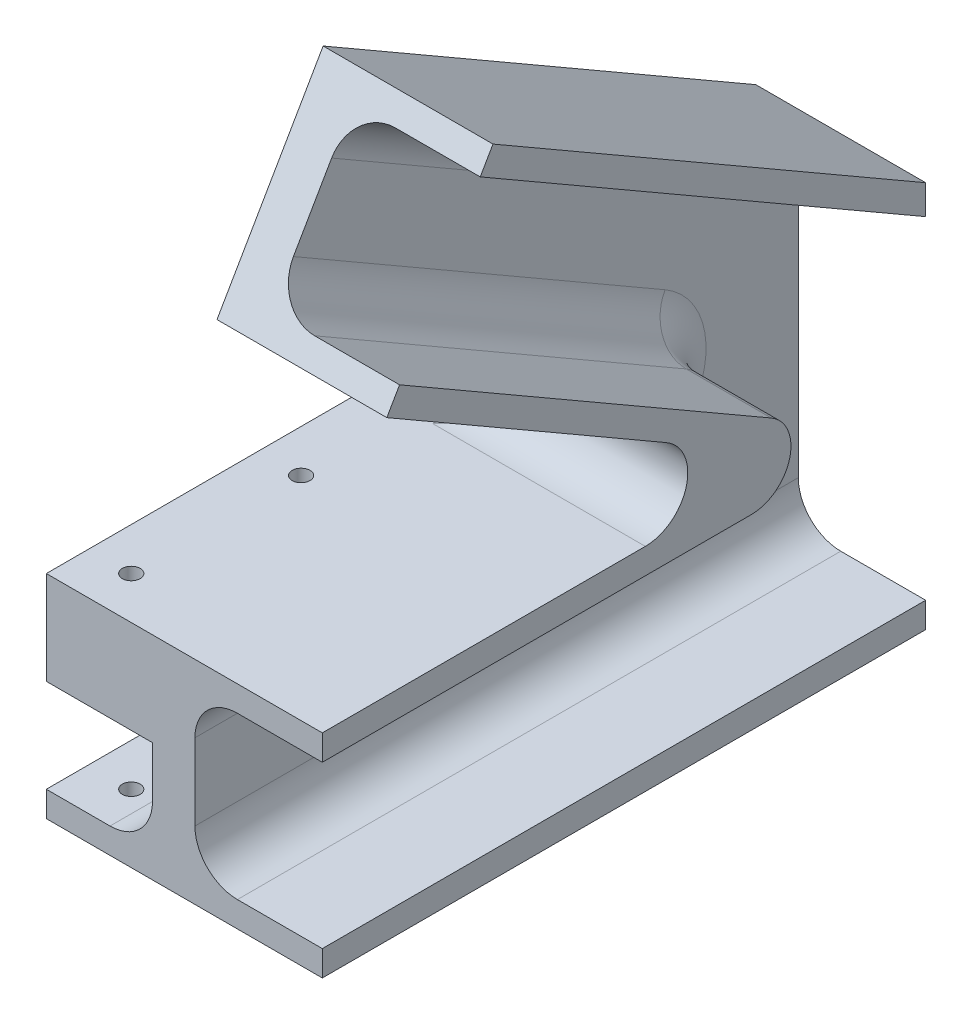
SolidWorks part; units mm, degrees
ref_plane "前视基准面" through (0, 0, 0) normal (0, 0, 1) x (1, 0, 0)
ref_plane "上视基准面" through (0, 0, 0) normal (0, 1, 0) x (1, 0, 0)
ref_plane "右视基准面" through (0, 0, 0) normal (1, 0, 0) x (0, 0, -1)
sketch "草图1" plane through (0, 0, 0) normal (1, 0, 0) x (0, 0, -1)
  line L0 (0, 0) -> (113.3975, 0)
  line L1 (113.3975, 0) -> (15.1924, 56.6987)
  line L2 (0, -50) -> (300, -50)
  line L3 (300, -50) -> (40.1924, 100)
  line L4 (0, 0) -> (0, -50)
  line L5 (40.1924, 100) -> (15.1924, 56.6987)
  line L6 (230.718, -10) -> (230.718, -50)
  line L7 (6, -6) -> (135.7898, -6)
  line L8 (135.7898, -6) -> (23.3885, 58.8949)
  line L10 (277.6077, -44) -> (42.3885, 91.8038)
  line L11 (6, -44) -> (277.6077, -44)
  line L13 (6, -6) -> (6, -44) construction
  line L14 (42.3885, 91.8038) -> (23.3885, 58.8949) construction
  line L15 (6, -6) -> (0, -6)
  line L16 (6, -44) -> (0, -44)
  line L17 (23.3885, 58.8949) -> (18.1924, 61.8949)
  line L18 (42.3885, 91.8038) -> (37.1924, 94.8038)
  line L19 (224.718, -6.5359) -> (224.718, -50)
  dimension "D7" = 6
  dimension "D1" = 50
  dimension "D2" = 30
  dimension "D3" = 300
  dimension "D4" = 300
  dimension "D5" = 40
  dimension "D6" = 6
extrude "凸台-拉伸1" add sketch "草图1" along normal blind 40 contours L8 L17 L5 L1 L0 L4 L15 L7 | L19 L3 L5 L18 L10 | L19 L11 L16 L4 L2 | L11 L19 L2 L6 | L10 L19 L11 L6 | L3 L19 L10 L6 region at (0, -1.5182, -56.6987) region at (0, -47, -112.359) region at (0, 43.6928, -131.7032) region at (0, -47, -227.718) region at (0, -29.5807, -227.6578) region at (0, -11.7321, -227.718)
extrude "凸台-拉伸2" add sketch "草图1<6>" along normal blind 10 contours L19 L10 L18 L5 L17 L8 L7 L15 L4 L16 L11 region at (0, -8.6413, -3)
sketch "草图1<6>" plane through (0, 0, 0) normal (1, 0, 0) x (0, 0, -1) same geometry as "草图1"
extrude "凸台-拉伸4" add sketch "草图1<9>" against normal blind 25 contours L19 L11 L16 L4 L2 region at (0, -47, -112.359)
sketch "草图1<9>" plane through (0, 0, 0) normal (1, 0, 0) x (0, 0, -1) same geometry as "草图1"
sketch "草图2" plane through (0, 0, 0) normal (-1, 0, 0) x (0, 0, 1)
  line L0 (0, 0) -> (-213.3975, 0)
  line L1 (-230.718, -10) -> (-40.1924, 100) construction
  line L2 (0, -6) -> (-223.7898, -6)
  line L3 (0, 0) -> (0, -44) construction
  line L4 (0, 0) -> (0, -6)
  line L5 (-213.3975, 0) -> (-223.7898, -6)
  dimension "D1" = 6
extrude "凸台-拉伸5" add sketch "草图2" along normal blind 25
fillet "圆角4" radius 10 2 edges at (0, 0, -163.3975) (20, 0, -113.3975)
fillet "圆角5" radius 10 2 edges at (0, -44, -112.359) (0, -6, -111.8949)
fillet "圆角6" radius 10 2 edges at (25, -44, -224.718) (25, -13.4641, -224.718)
fillet "圆角7" radius 10 1 edges at (19, -10, -230.718)
sketch "草图3" plane through (40, 0, 0) normal (1, 0, 0) x (0, 0, -1)
  line L0 (135.7898, -6) -> (18.1924, 61.8949) construction
  line L1 (135.7898, -6) -> (0, -6) construction
  line L2 (101.077, -6) -> (135.7898, -6)
  line L3 (135.7898, -6) -> (105.7276, 11.3564)
  arc A0 (105.7276, 11.3564) -> (101.077, -6) centre (101.077, 3.3013) cw
  arc A1 (76.077, 0) -> (81.077, 18.6603) centre (76.077, 10) ccw construction
  dimension "D1" = 25
extrude "切除-拉伸1" cut sketch "草图3" against normal blind 30
fillet "圆角11" radius 10 8 edges at (10, 36.6256, -61.96) (10, 0.8939, -110.0613) (10, -44, -107.359) (10, -41.0711, -221.789) (10, -26.6188, -224.718) (10, -14.2376, -223.3782) (10, -6, -50.5385) (10, 42.1132, -128.4552)
sketch "草图5" plane through (0, 0, 0) normal (0, 1, 0) x (1, 0, 0)
  line L0 (40, 0) -> (-25, 0) construction
  line L3 (-25, 0) -> (-25, 213.3975) construction
  circle A2 centre (-15, 10) radius 2.1
  circle A3 centre (-15, 50) radius 2.1
  circle A4 centre (-15, 90) radius 2.1
  circle A5 centre (-15, 130) radius 2.1
  dimension "D2" = 10
  dimension "D1" = 10
  dimension "D3" = 4.2
  dimension "D4" = 4
  dimension "D5" = 40
extrude "切除-拉伸2" cut sketch "草图5" against normal through all
sketch "草图6" plane through (0, 0, 0) normal (0, 1, 0) x (1, 0, 0)
  line L0 (40, 225.718) -> (40, 40.1924) construction
  line L1 (-25, 231.518) -> (40, 231.518)
  line L2 (-25, 231.518) -> (-25, 142.1)
  line L3 (-25, 142.1) -> (40, 142.1)
  line L4 (40, 231.518) -> (40, 142.1)
  line L5 (-25, 231.518) -> (40, 142.1) construction
  line L6 (-25, 142.1) -> (40, 231.518) construction
  line L7 (-25, 0) -> (-25, 213.3975) construction
  circle A0 centre (-15, 130) radius 2.1 construction
  point P0 (7.5, 186.809)
  dimension "D1" = 12.1
extrude "切除-拉伸3" cut sketch "草图6" against normal through all
extrude "切除-拉伸4" cut sketch "草图6<2>" along normal through all
sketch "草图6<2>" plane through (0, 0, 0) normal (0, 1, 0) x (1, 0, 0) same geometry as "草图6"
sketch "草图8" plane through (0, -6, 0) normal (0, -1, 0) x (1, 0, 0)
  line L0 (-25, 0) -> (-25, -142.1)
  line L1 (-25, -142.1) -> (0, -142.1)
  line L2 (0, -142.1) -> (0, 0)
  line L3 (0, 0) -> (-25, 0)
  dimension "D1" = 25
extrude "凸台-拉伸6" add sketch "草图8" along normal blind 16
extrude "切除-拉伸5" cut sketch "草图5<2>" against normal through all
sketch "草图5<2>" plane through (0, 0, 0) normal (0, 1, 0) x (1, 0, 0) same geometry as "草图5"
